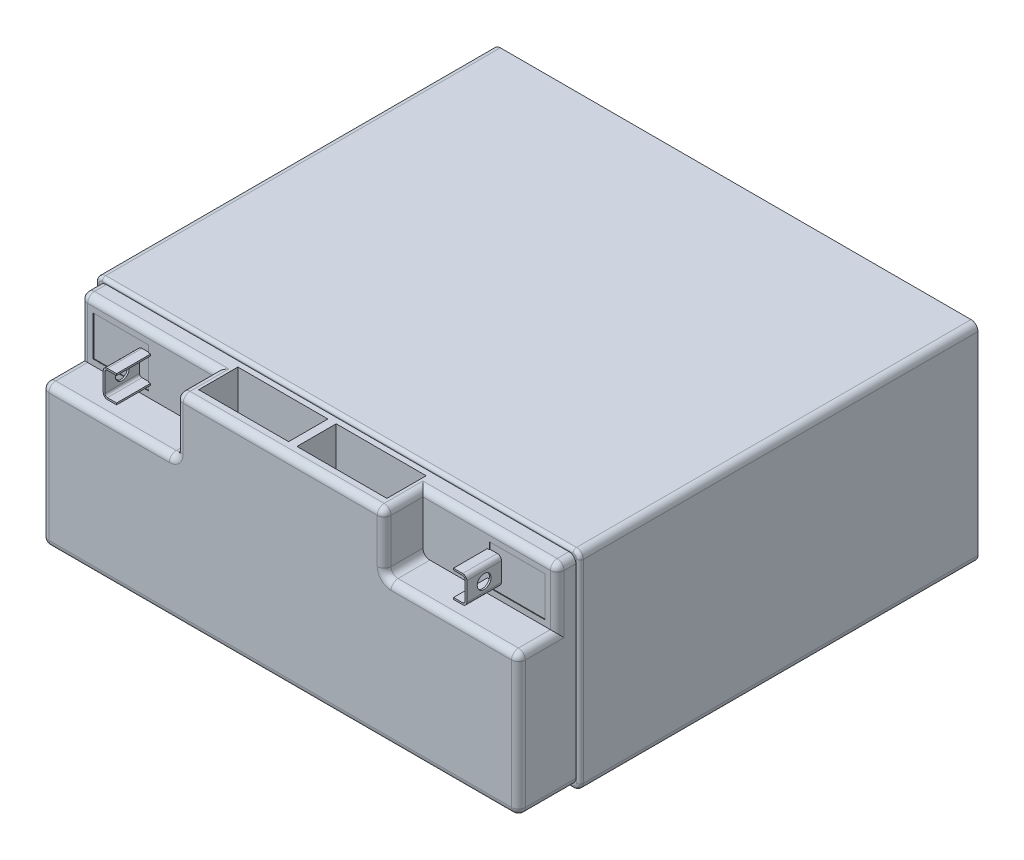
SolidWorks part; units mm, degrees
ref_plane "Front Plane" through (0, 0, 0) normal (0, 0, 1) x (1, 0, 0)
ref_plane "Top Plane" through (0, 0, 0) normal (0, 1, 0) x (1, 0, 0)
ref_plane "Right Plane" through (0, 0, 0) normal (1, 0, 0) x (0, 0, -1)
ref_plane "Plane1" through (0, -62.2132, 0) normal (0, -1, 0) x (1, 0, 0)
sketch "Sketch1" plane through (0, -62.2132, 0) normal (0, -1, 0) x (1, 0, 0)
  line L0 (-33.1131, 0) -> (144.6869, 0)
  line L1 (144.6869, 0) -> (144.6869, 146.05)
  line L2 (144.6869, 146.05) -> (-33.1131, 146.05)
  line L3 (-33.1131, 146.05) -> (-33.1131, 0)
  dimension "D1" = 177.8
  dimension "D2" = 146.05
extrude "Extrude1" add sketch "Sketch1" against normal blind 76.2
sketch "Sketch2" plane through (0, 0, 146.05) normal (0, 0, 1) x (1, 0, 0)
  line L0 (143.2096, 12.5094) -> (143.2096, -60.7358)
  line L1 (143.2096, -60.7358) -> (-31.6357, -60.7358)
  line L2 (-31.6357, -60.7358) -> (-31.6357, 12.5094)
  line L3 (-31.6357, 12.5094) -> (143.2096, 12.5094)
  line L4 (-33.1131, 13.9868) -> (-33.1131, -62.2132) construction
  line L5 (144.6869, -62.2132) -> (-33.1131, -62.2132) construction
  dimension "D1" = 1.4774
  dimension "D2" = 176.3226
  dimension "D3" = 1.4774
  dimension "D4" = 74.7226
extrude "Extrude2" add sketch "Sketch2" along normal blind 21.082
sketch "Sketch3" plane through (-31.6357, 0, 0) normal (-1, 0, 0) x (0, 0, 1)
  line L0 (152.908, 12.5094) -> (152.908, -8.8266)
  line L1 (152.908, -8.8266) -> (167.132, -8.8266)
  line L2 (167.132, -8.8266) -> (167.132, 12.5094)
  line L3 (167.132, 12.5094) -> (152.908, 12.5094)
  line L4 (167.132, 12.5094) -> (167.132, -60.7358) construction
  line L5 (167.132, -60.7358) -> (146.05, -60.7358) construction
  dimension "D1" = 14.224
  dimension "D2" = 51.9092
  dimension "D3" = 73.2452
extrude "Extrude3" cut sketch "Sketch3" against normal blind 49.276
sketch "Sketch4" plane through (0, 0, 152.908) normal (0, 0, 1) x (1, 0, 0)
  line L0 (-27.0726, 7.9428) -> (-27.0726, -6.6776)
  line L1 (-27.0726, -6.6776) -> (-6.7872, -6.6776)
  line L2 (-6.7872, -6.6776) -> (-6.7872, -4.5374)
  line L3 (-6.7872, -4.5374) -> (-10.918, -4.5374)
  line L4 (-10.918, -4.5374) -> (-10.918, 5.3949)
  line L5 (-10.918, 5.3949) -> (-6.7872, 5.3949)
  line L6 (-6.7872, 5.3949) -> (-6.7872, 7.9428)
  line L7 (-6.7872, 7.9428) -> (-27.0726, 7.9428)
  line L8 (-31.6357, 12.5094) -> (-31.6357, -8.8266) construction
  line L9 (17.6403, -8.8266) -> (-31.6357, -8.8266) construction
  dimension "D1" = 4.5631
  dimension "D2" = 20.7177
  dimension "D3" = 24.8485
  dimension "D4" = 2.149
  dimension "D5" = 4.2892
  dimension "D6" = 14.2215
  dimension "D7" = 16.7694
extrude "Extrude4" cut sketch "Sketch4" against normal blind 0.254
sketch "Sketch5" plane through (0, 0, 152.908) normal (0, 0, 1) x (1, 0, 0)
  line L0 (-6.018, -4.5374) -> (-10.918, -4.5374)
  line L1 (-10.918, -4.5374) -> (-10.918, 5.3949)
  line L2 (-10.918, 5.3949) -> (-6.018, 5.3949)
  line L3 (-6.018, 5.3949) -> (-6.018, -4.5374)
  line L4 (-31.6357, 12.5094) -> (-31.6357, -8.8266) construction
  line L5 (17.6403, -8.8266) -> (-31.6357, -8.8266) construction
  dimension "D1" = 20.7177
  dimension "D2" = 25.6177
  dimension "D3" = 4.2892
  dimension "D4" = 14.2215
extrude "Extrude5" add sketch "Sketch5" along normal blind 12.446
sketch "Sketch6" plane through (-6.018, 0, 0) normal (1, 0, 0) x (0, 0, -1)
  line L0 (-152.908, -3.9265) -> (-152.908, 4.784)
  line L1 (-152.908, 4.784) -> (-165.354, 4.784)
  line L2 (-165.354, 4.784) -> (-165.354, -3.9265)
  line L3 (-165.354, -3.9265) -> (-152.908, -3.9265)
  line L4 (-165.354, -4.5374) -> (-165.354, 5.3949) construction
  line L5 (-165.354, -4.5374) -> (-152.908, -4.5374) construction
  dimension "D1" = 12.446
  dimension "D2" = 0.6109
  dimension "D3" = 9.3214
extrude "Extrude6" cut sketch "Sketch6" against normal blind 4.289
sketch "Sketch7" plane through (0, 0, 152.908) normal (0, 0, 1) x (1, 0, 0)
  line L0 (-10.3071, 4.784) -> (-10.3071, -3.9265)
  line L1 (-10.3071, -3.9265) -> (-6.7872, -3.9265)
  line L2 (-6.7872, -3.9265) -> (-6.7872, 4.784)
  line L3 (-6.7872, 4.784) -> (-10.3071, 4.784)
  line L4 (-31.6357, 12.5094) -> (-31.6357, -8.8266) construction
  line L5 (17.6403, -8.8266) -> (-31.6357, -8.8266) construction
  dimension "D1" = 21.3286
  dimension "D2" = 24.8485
  dimension "D3" = 4.9001
  dimension "D4" = 13.6106
extrude "Extrude7" cut sketch "Sketch7" against normal blind 0.254
sketch "Sketch8" plane through (0, 12.5094, 0) normal (0, 1, 0) x (-1, 0, 0)
  line L0 (-143.2096, 152.908) -> (-93.9336, 152.908)
  line L1 (-93.9336, 152.908) -> (-93.9336, 167.132)
  line L2 (-93.9336, 167.132) -> (-143.2096, 167.132)
  line L3 (-143.2096, 167.132) -> (-143.2096, 152.908)
  line L4 (31.6357, 152.908) -> (31.6357, 146.05) construction
  line L5 (-143.2096, 146.05) -> (31.6357, 146.05) construction
  dimension "D1" = 125.5692
  dimension "D2" = 174.8452
  dimension "D3" = 6.858
  dimension "D4" = 21.082
extrude "Extrude8" cut sketch "Sketch8" against normal blind 21.336
sketch "Sketch9" plane through (0, 0, 152.908) normal (0, 0, 1) x (1, 0, 0)
  line L0 (118.361, 5.3949) -> (122.4919, 5.3949)
  line L1 (122.4919, 5.3949) -> (122.4919, -4.5374)
  line L2 (122.4919, -4.5374) -> (118.361, -4.5374)
  line L3 (118.361, -4.5374) -> (118.361, -6.6776)
  line L4 (118.361, -6.6776) -> (138.6465, -6.6776)
  line L5 (138.6465, -6.6776) -> (138.6465, 7.9428)
  line L6 (138.6465, 7.9428) -> (118.361, 7.9428)
  line L7 (118.361, 7.9428) -> (118.361, 5.3949)
  line L8 (93.9336, -8.8266) -> (93.9336, 12.5094) construction
  line L9 (143.2096, -8.8266) -> (93.9336, -8.8266) construction
  dimension "D1" = 24.4275
  dimension "D2" = 28.5583
  dimension "D3" = 44.7129
  dimension "D4" = 2.149
  dimension "D5" = 4.2892
  dimension "D6" = 14.2215
  dimension "D7" = 16.7694
extrude "Extrude9" cut sketch "Sketch9" against normal blind 0.254
sketch "Sketch10" plane through (0, 0, 152.908) normal (0, 0, 1) x (1, 0, 0)
  line L0 (122.4919, -4.5374) -> (117.5919, -4.5374)
  line L1 (117.5919, -4.5374) -> (117.5919, 5.3949)
  line L2 (117.5919, 5.3949) -> (122.4919, 5.3949)
  line L3 (122.4919, 5.3949) -> (122.4919, -4.5374)
  line L4 (93.9336, -8.8266) -> (93.9336, 12.5094) construction
  line L5 (143.2096, -8.8266) -> (93.9336, -8.8266) construction
  dimension "D1" = 23.6583
  dimension "D2" = 28.5583
  dimension "D3" = 4.2892
  dimension "D4" = 14.2215
extrude "Extrude10" add sketch "Sketch10" along normal blind 12.446
sketch "Sketch11" plane through (117.5919, 0, 0) normal (-1, 0, 0) x (0, 0, 1)
  line L0 (152.908, 4.784) -> (152.908, -3.9265)
  line L1 (152.908, -3.9265) -> (165.354, -3.9265)
  line L2 (165.354, -3.9265) -> (165.354, 4.784)
  line L3 (165.354, 4.784) -> (152.908, 4.784)
  line L4 (165.354, 5.3949) -> (165.354, -4.5374) construction
  line L5 (165.354, -4.5374) -> (152.908, -4.5374) construction
  dimension "D1" = 12.446
  dimension "D2" = 0.6109
  dimension "D3" = 9.3214
extrude "Extrude11" cut sketch "Sketch11" against normal blind 4.289
sketch "Sketch12" plane through (0, 0, 152.908) normal (0, 0, 1) x (1, 0, 0)
  line L0 (121.8809, 4.784) -> (118.361, 4.784)
  line L1 (118.361, 4.784) -> (118.361, -3.9265)
  line L2 (118.361, -3.9265) -> (121.8809, -3.9265)
  line L3 (121.8809, -3.9265) -> (121.8809, 4.784)
  line L4 (93.9336, -8.8266) -> (93.9336, 12.5094) construction
  line L5 (143.2096, -8.8266) -> (93.9336, -8.8266) construction
  dimension "D1" = 24.4275
  dimension "D2" = 27.9474
  dimension "D3" = 4.9001
  dimension "D4" = 13.6106
extrude "Extrude12" cut sketch "Sketch12" against normal blind 0.254
sketch "Sketch13" plane through (0, 12.5094, 0) normal (0, 1, 0) x (-1, 0, 0)
  line L0 (-90.3309, 148.1138) -> (-57.3109, 148.1138)
  line L1 (-57.3109, 148.1138) -> (-57.3109, 162.5135)
  line L2 (-57.3109, 162.5135) -> (-90.3309, 162.5135)
  line L3 (-90.3309, 162.5135) -> (-90.3309, 148.1138)
  line L4 (31.6357, 152.908) -> (31.6357, 146.05) construction
  line L5 (-143.2096, 146.05) -> (31.6357, 146.05) construction
  dimension "D1" = 88.9466
  dimension "D2" = 121.9666
  dimension "D3" = 2.0638
  dimension "D4" = 16.4635
extrude "Extrude13" cut sketch "Sketch13" against normal blind 19.05
sketch "Sketch14" plane through (0, 12.5094, 0) normal (0, 1, 0) x (-1, 0, 0)
  line L0 (-54.2629, 148.1138) -> (-21.2429, 148.1138)
  line L1 (-21.2429, 148.1138) -> (-21.2429, 162.5135)
  line L2 (-21.2429, 162.5135) -> (-54.2629, 162.5135)
  line L3 (-54.2629, 162.5135) -> (-54.2629, 148.1138)
  line L4 (31.6357, 152.908) -> (31.6357, 146.05) construction
  line L5 (-143.2096, 146.05) -> (31.6357, 146.05) construction
  dimension "D1" = 52.8786
  dimension "D2" = 85.8986
  dimension "D3" = 2.0638
  dimension "D4" = 16.4635
extrude "Extrude14" cut sketch "Sketch14" against normal blind 19.05
sketch "Sketch15" plane through (0, -60.7358, 0) normal (0, -1, 0) x (1, 0, 0)
  line L0 (56.8496, 162.8434) -> (56.8496, 147.6421)
  line L1 (56.8496, 147.6421) -> (120.3496, 147.6421)
  line L2 (120.3496, 147.6421) -> (120.3496, 162.8434)
  line L3 (120.3496, 162.8434) -> (56.8496, 162.8434)
  line L4 (-31.6357, 167.132) -> (-31.6357, 146.05) construction
  line L5 (-31.6357, 167.132) -> (143.2096, 167.132) construction
  dimension "D1" = 88.4852
  dimension "D2" = 151.9852
  dimension "D3" = 4.2886
  dimension "D4" = 19.4899
extrude "Extrude15" cut sketch "Sketch15" against normal blind 19.558
sketch "Sketch16" plane through (0, -60.7358, 0) normal (0, -1, 0) x (1, 0, 0)
  line L0 (-8.7757, 162.8434) -> (-8.7757, 147.6421)
  line L1 (-8.7757, 147.6421) -> (54.7243, 147.6421)
  line L2 (54.7243, 147.6421) -> (54.7243, 162.8434)
  line L3 (54.7243, 162.8434) -> (-8.7757, 162.8434)
  line L4 (-31.6357, 167.132) -> (-31.6357, 146.05) construction
  line L5 (-31.6357, 167.132) -> (143.2096, 167.132) construction
  dimension "D1" = 22.86
  dimension "D2" = 86.36
  dimension "D3" = 4.2886
  dimension "D4" = 19.4899
extrude "Extrude16" cut sketch "Sketch16" against normal blind 19.558
hole_wizard "Hole1" positions "Sketch18" profile "Sketch17" legacy
sketch "Sketch18" plane through (122.4919, 0, 0) normal (1, 0, 0) x (0, 0, -1)
  point P0 (-159.004, 0.4288)
sketch "Sketch17" plane through (122.4919, 0.4288, 159.004) normal (0, 1, 0) x (0, 0, -1)
  line L0 (0, 0) -> (0, 0.6109)
  line L1 (0, 0.6109) -> (2.54, 0.6109)
  line L2 (2.54, 0.6109) -> (2.54, 0)
  line L3 (2.54, 0) -> (0, 0)
  line L4 (0, 110) -> (0, -10) construction
  dimension "Diameter" = 5.08
  dimension "Depth" = 0.6109
hole_wizard "Hole2" positions "Sketch20" profile "Sketch19" legacy
sketch "Sketch20" plane through (-10.3071, 0, 0) normal (1, 0, 0) x (0, 0, -1)
  point P0 (-159.004, 0.4288)
sketch "Sketch19" plane through (-10.3071, 0.4288, 159.004) normal (0, 1, 0) x (0, 0, -1)
  line L0 (0, 0) -> (0, 22.806)
  line L1 (0, 22.806) -> (2.54, 22.806)
  line L2 (2.54, 22.806) -> (2.54, 0)
  line L3 (2.54, 0) -> (0, 0)
  line L4 (0, 110) -> (0, -10) construction
  dimension "Diameter" = 5.08
  dimension "Depth" = 22.806
fillet "Fillet1" radius 2.54 1 edges at (144.6869, 13.9868, 73.025) tangent propagation no
fillet "Fillet2" radius 2.54 1 edges at (-33.1131, -62.2132, 73.025) tangent propagation no
fillet "Fillet3" radius 2.54 1 edges at (144.6869, -62.2132, 73.025) tangent propagation no
fillet "Fillet4" radius 2.54 1 edges at (93.9336, -8.8266, 160.02) tangent propagation no
fillet "Fillet5" radius 2.54 1 edges at (-33.1131, 13.9868, 73.025) tangent propagation no
fillet "Fillet6" radius 2.54 1 edges at (17.6403, -8.8266, 160.02) tangent propagation no
fillet "Fillet7" radius 0.9131 1 edges at (-10.3071, -3.9265, 159.004) tangent propagation no
fillet "Fillet8" radius 0.9131 1 edges at (121.8809, 4.784, 159.004) tangent propagation no
fillet "Fillet9" radius 0.9131 1 edges at (-10.3071, 4.784, 159.004) tangent propagation no
fillet "Fillet10" radius 0.9131 1 edges at (121.8809, -3.9265, 159.004) tangent propagation no
fillet "Fillet11" radius 1.27 8 edges at (143.943, 13.2428, 146.05) (55.7869, 13.9868, 146.05) (144.6869, -24.1132, 146.05) (-32.3691, 13.2428, 146.05) (143.943, -61.4693, 146.05) (-33.1131, -24.1132, 146.05) (55.7869, -62.2132, 146.05) (-32.3691, -61.4693, 146.05) tangent propagation no
fillet "Fillet12" radius 1.524 1 edges at (-10.918, 5.3949, 159.004) tangent propagation no
fillet "Fillet13" radius 1.524 1 edges at (122.4919, -4.5374, 159.004) tangent propagation no
fillet "Fillet14" radius 1.524 1 edges at (-10.918, -4.5374, 159.004) tangent propagation no
fillet "Fillet15" radius 1.524 1 edges at (122.4919, 5.3949, 159.004) tangent propagation no
fillet "Fillet16" radius 2.54 22 edges at (143.2096, -60.7358, 156.5802) (143.2096, 12.5094, 149.4682) (143.2096, 1.8414, 152.908) (-31.6357, -60.7358, 156.5802) (55.7869, -60.7358, 167.132) (143.2096, -34.7812, 167.132) (143.2096, -8.8266, 160.02) (118.5716, 12.5094, 152.908) (-31.6357, 12.5094, 149.4682) (-31.6357, 1.8414, 152.908) (-31.6357, -8.8266, 160.02) (-31.6357, -34.7812, 167.132) (93.9336, 3.1114, 167.132) (119.8416, -8.8266, 167.132) (94.6775, -8.0826, 167.132) (93.9336, 12.5094, 160.02) (-6.9977, 12.5094, 152.908) (17.6403, 3.1114, 167.132) (-8.2677, -8.8266, 167.132) (16.8964, -8.0826, 167.132) (55.7869, 12.5094, 167.132) (17.6403, 12.5094, 160.02)
sketch "Sketch21" plane through (0, 13.9868, 0) normal (0, 1, 0) x (1, 0, 0)
  text T0 "Battery\r\n"
